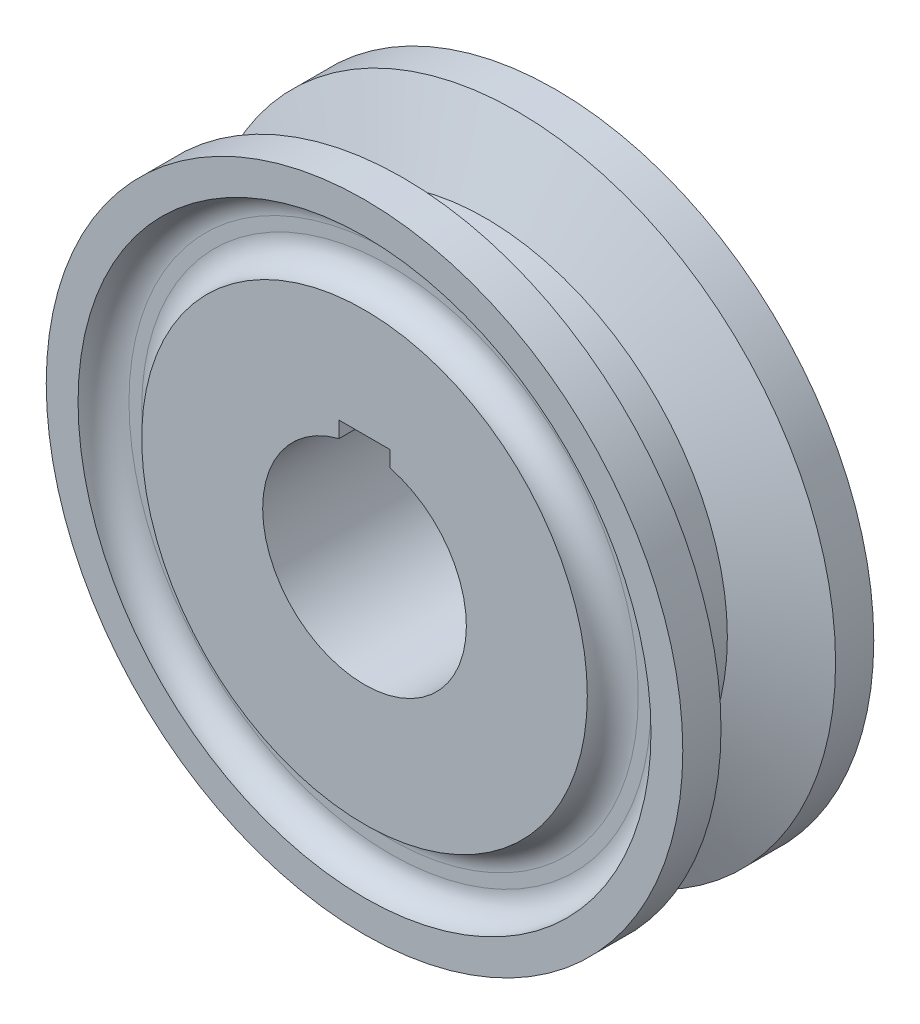
SolidWorks part; units mm, degrees
material "Cast Alloy Steel"
ref_plane "Front Plane" through (0, 0, 0) normal (0, 0, 1) x (1, 0, 0)
ref_plane "Top Plane" through (0, 0, 0) normal (0, 1, 0) x (1, 0, 0)
ref_plane "Right Plane" through (0, 0, 0) normal (1, 0, 0) x (0, 0, -1)
sketch "Sketch1" plane through (0, 0, 0) normal (1, 0, 0) x (0, 0, -1)
  line L0 (-350.1374, 0) -> (17156.732, 0) construction
  line L1 (0, 0) -> (0, 19) construction
  line L2 (4.5, 25) -> (7.5, 25)
  line L3 (7.5, 25) -> (7.5, 0)
  line L4 (7.5, 0) -> (0, 0)
  line L5 (4.5, 25) -> (2, 19)
  line L6 (2, 19) -> (-2, 19)
  line L7 (-4.5, 25) -> (-2, 19)
  line L8 (-7.5, 25) -> (-7.5, 0)
  line L9 (-4.5, 25) -> (-7.5, 25)
  line L10 (0, 0) -> (-7.5, 0)
  dimension "D1" = 25
  dimension "D2" = 7.5
  dimension "D3" = 2
  dimension "D4" = 3
  dimension "D5" = 6
revolve "Revolve1" add sketch "Sketch1" angle 360 about L0
sketch "Sketch2" plane through (0, 0, 7.5) normal (0, 0, 1) x (1, 0, 0)
  line L1 (-2, 9) -> (2, 9)
  line L2 (-2, 9) -> (-2, 7.746)
  line L4 (2, 9) -> (2, 7.746)
  arc A0 (-2, 7.746) -> (2, 7.746) centre (0, 0) ccw
  point P3 (0, 8)
  dimension "D1" = 16
  dimension "D2" = 4
  dimension "D3" = 9
  dimension "D4" = 1.254
extrude "Cut-Extrude1" cut sketch "Sketch2" against normal through all
sketch "Sketch3" plane through (0, 0, 7.5) normal (0, 0, 1) x (1, 0, 0)
  circle A0 centre (0, 0) radius 22.5
  circle A1 centre (0, 0) radius 17.5
  dimension "D1" = 45
  dimension "D2" = 35
extrude "Cut-Extrude2" cut sketch "Sketch3" against normal blind 2
sketch "Sketch4" plane through (0, 0, -7.5) normal (0, 0, -1) x (-1, 0, 0)
  circle A0 centre (0, 0) radius 22.5
  circle A1 centre (0, 0) radius 17.5
  dimension "D1" = 45
  dimension "D2" = 35
extrude "Cut-Extrude3" cut sketch "Sketch4" against normal blind 2
fillet "Fillet1" radius 2 4 edges at (22.5, 0, 5.5) (17.5, 0, 5.5) (-22.5, 0, -5.5) (-17.5, 0, -5.5)
